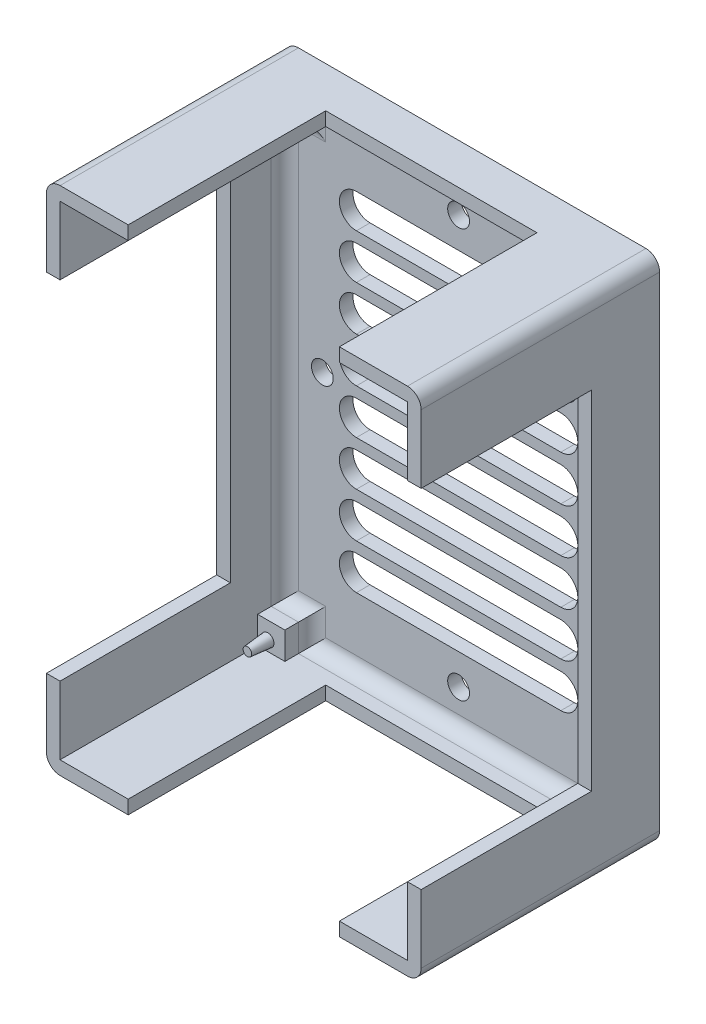
SolidWorks part; units mm, degrees
ref_plane "Front Plane" through (0, 0, 0) normal (1, 0, 0) x (0, 1, 0)
ref_plane "Top Plane" through (0, 0, 0) normal (0, 0, 1) x (0, 1, 0)
ref_plane "Right Plane" through (0, 0, 0) normal (0, 1, 0) x (-1, 0, 0)
sketch "Sketch1" plane through (0, 0, 0) normal (0, 0, 1) x (0, 1, 0)
  line L1 (0, 0) -> (71, 0)
  line L2 (0, 0) -> (0, 51)
  line L3 (0, 51) -> (71, 51)
  line L4 (71, 0) -> (71, 51)
  dimension "D1" = 71
  dimension "D2" = 51
extrude "Boss-Extrude1" add sketch "Sketch1" along normal blind 33
shell "Shell1" thickness 2 removed face at (-25.5, 35.5, 33) outward yes
sketch "Sketch3" plane through (-51, 0, 0) normal (1, 0, 0) x (0, 1, 0)
  line L0 (71, 33) -> (71, 0) construction
  line L1 (0, 4) -> (4, 4)
  line L2 (0, 4) -> (0, 0)
  line L3 (0, 0) -> (4, 0)
  line L4 (71, 4) -> (71, 0)
  line L5 (0, 33) -> (0, 0) construction
  line L7 (4, 4) -> (4, 0)
  line L8 (67, 4) -> (67, 0)
  line L9 (67, 4) -> (71, 4)
  line L10 (67, 0) -> (71, 0)
  line L11 (71, 0) -> (0, 0) construction
  dimension "D2" = 4
  dimension "D3" = 4
extrude "Boss-Extrude2" add sketch "Sketch3" along normal blind 4
ref_plane "Plane5" through (-25.5, 0, 0) normal (1, 0, 0) x (0, 0, -1)
ref_plane "Plane6" through (0, 35.5, 0) normal (0, 1, 0) x (1, 0, 0)
mirror "Mirror1" about plane through (-25.5, 0, 0) normal (1, 0, 0) of "Boss-Extrude2"
fillet "Fillet1" radius 2 16 edges at (-25.5, 0, 0) (-47, 2, 0) (-49, 4, 0) (-51, 35.5, 0) (-49, 67, 0) (-47, 69, 0) (-25.5, 71, 0) (-4, 69, 0) (-2, 67, 0) (0, 35.5, 0) (-2, 4, 0) (-4, 2, 0) (-53, -2, 15.5) (2, -2, 15.5) (-53, 73, 15.5) (2, 73, 15.5)
sketch "Sketch4" plane through (0, 0, 0) normal (0, 0, 1) x (1, 0, 0)
  line L0 (-40.5, 58.5) -> (-10.5, 58.5) construction
  line L1 (-40.5, 61) -> (-10.5, 61)
  line L2 (-40.5, 56) -> (-10.5, 56)
  line L3 (-6, 69) -> (-45, 69) construction
  line L4 (-25.5, 69) -> (-25.5, 2) construction
  line L5 (-45, 2) -> (-6, 2) construction
  line L6 (-40.5, 51.9286) -> (-10.5, 51.9286) construction
  line L7 (-40.5, 54.4286) -> (-10.5, 54.4286)
  line L8 (-40.5, 49.4286) -> (-10.5, 49.4286)
  line L9 (-40.5, 45.3571) -> (-10.5, 45.3571) construction
  line L10 (-40.5, 47.8571) -> (-10.5, 47.8571)
  line L11 (-40.5, 42.8571) -> (-10.5, 42.8571)
  line L12 (-40.5, 38.7857) -> (-10.5, 38.7857) construction
  line L13 (-40.5, 41.2857) -> (-10.5, 41.2857)
  line L14 (-40.5, 36.2857) -> (-10.5, 36.2857)
  line L15 (-40.5, 32.2143) -> (-10.5, 32.2143) construction
  line L16 (-40.5, 34.7143) -> (-10.5, 34.7143)
  line L17 (-40.5, 29.7143) -> (-10.5, 29.7143)
  line L18 (-40.5, 25.6429) -> (-10.5, 25.6429) construction
  line L19 (-40.5, 28.1429) -> (-10.5, 28.1429)
  line L20 (-40.5, 23.1429) -> (-10.5, 23.1429)
  line L21 (-40.5, 19.0714) -> (-10.5, 19.0714) construction
  line L22 (-40.5, 21.5714) -> (-10.5, 21.5714)
  line L23 (-40.5, 16.5714) -> (-10.5, 16.5714)
  line L24 (-40.5, 12.5) -> (-10.5, 12.5) construction
  line L25 (-40.5, 15) -> (-10.5, 15)
  line L26 (-40.5, 10) -> (-10.5, 10)
  line L27 (-45.5, 65.5) -> (-5.5, 65.5) construction
  line L28 (-45.5, 65.5) -> (-45.5, 5.5) construction
  line L29 (-45.5, 5.5) -> (-5.5, 5.5) construction
  line L30 (-5.5, 65.5) -> (-5.5, 5.5) construction
  line L31 (-49, 35.5) -> (-5, 35.5) construction
  line L32 (-49, 65) -> (-49, 6) construction
  arc A0 (-40.5, 61) -> (-40.5, 56) centre (-40.5, 58.5) ccw
  arc A1 (-10.5, 56) -> (-10.5, 61) centre (-10.5, 58.5) ccw
  arc A2 (-40.5, 54.4286) -> (-40.5, 49.4286) centre (-40.5, 51.9286) ccw
  arc A3 (-10.5, 49.4286) -> (-10.5, 54.4286) centre (-10.5, 51.9286) ccw
  arc A4 (-40.5, 47.8571) -> (-40.5, 42.8571) centre (-40.5, 45.3571) ccw
  arc A5 (-10.5, 42.8571) -> (-10.5, 47.8571) centre (-10.5, 45.3571) ccw
  arc A6 (-40.5, 41.2857) -> (-40.5, 36.2857) centre (-40.5, 38.7857) ccw
  arc A7 (-10.5, 36.2857) -> (-10.5, 41.2857) centre (-10.5, 38.7857) ccw
  arc A8 (-40.5, 34.7143) -> (-40.5, 29.7143) centre (-40.5, 32.2143) ccw
  arc A9 (-10.5, 29.7143) -> (-10.5, 34.7143) centre (-10.5, 32.2143) ccw
  arc A10 (-40.5, 28.1429) -> (-40.5, 23.1429) centre (-40.5, 25.6429) ccw
  arc A11 (-10.5, 23.1429) -> (-10.5, 28.1429) centre (-10.5, 25.6429) ccw
  arc A12 (-40.5, 21.5714) -> (-40.5, 16.5714) centre (-40.5, 19.0714) ccw
  arc A13 (-10.5, 16.5714) -> (-10.5, 21.5714) centre (-10.5, 19.0714) ccw
  arc A14 (-40.5, 15) -> (-40.5, 10) centre (-40.5, 12.5) ccw
  arc A15 (-10.5, 10) -> (-10.5, 15) centre (-10.5, 12.5) ccw
  circle A20 centre (-25.5, 5.5) radius 1.6
  circle A21 centre (-45.5, 35.5) radius 1.6
  circle A22 centre (-5.5, 35.5) radius 1.6
  circle A23 centre (-25.5, 65.5) radius 1.6
  point P2 (-25.5, 58.5)
  point P16 (-25.5, 51.9286)
  point P23 (-25.5, 45.3571)
  point P30 (-25.5, 38.7857)
  point P37 (-25.5, 32.2143)
  point P44 (-25.5, 25.6429)
  point P51 (-25.5, 19.0714)
  point P58 (-25.5, 12.5)
  dimension "D8" = 3.2
  dimension "D1" = 8
  dimension "D2" = 8
  dimension "D3" = 8
  dimension "D4" = 5
  dimension "D5" = 30
  dimension "D6" = 60
  dimension "D7" = 40
extrude "Cut-Extrude1" cut sketch "Sketch4" against normal up to next
sketch "Sketch5" plane through (2, 0, 0) normal (1, 0, 0) x (0, 1, 0)
  line L0 (0, 33) -> (71, 33) construction
  line L1 (10, 33) -> (61, 33)
  line L2 (10, 33) -> (10, 8)
  line L3 (10, 8) -> (61, 8)
  line L4 (61, 33) -> (61, 8)
  line L5 (35.5, 33) -> (35.5, -2) construction
  line L6 (0, -2) -> (71, -2) construction
  line L7 (71, -2) -> (71, 33) construction
  point P10 (0, 0)
  point P11 (60.1318, 13.1857)
  dimension "D1" = 10
  dimension "D2" = 10
extrude "Cut-Extrude2" cut sketch "Sketch5" against normal through all
sketch "Sketch6" plane through (0, -2, 0) normal (0, -1, 0) x (1, 0, 0)
  line L0 (-51, 33) -> (0, 33) construction
  line L1 (-41, 33) -> (-10, 33)
  line L2 (-41, 33) -> (-41, 4)
  line L3 (-41, 4) -> (-10, 4)
  line L4 (-10, 33) -> (-10, 4)
  line L5 (-25.5, 33) -> (-25.5, -2) construction
  line L6 (-51, -2) -> (0, -2) construction
  line L7 (0, -2) -> (0, 33) construction
  point P10 (0, 0)
  dimension "D1" = 6
  dimension "D2" = 10
extrude "Cut-Extrude3" cut sketch "Sketch6" against normal through all
sketch "Sketch7" plane through (0, 0, 4) normal (0, 0, 1) x (1, 0, 0)
  line L0 (-49.5, 35.5) -> (-1.5, 35.5) construction
  line L1 (-49.5, 69.5) -> (-1.5, 69.5) construction
  line L2 (-49.5, 69.5) -> (-49.5, 1.5) construction
  line L3 (-49.5, 1.5) -> (-1.5, 1.5) construction
  line L4 (-1.5, 69.5) -> (-1.5, 1.5) construction
  line L5 (-41, 71) -> (-10, 71) construction
  line L6 (-10, 0) -> (-41, 0) construction
  line L7 (-25.5, 69.5) -> (-25.5, 1.5) construction
  line L8 (0, 61) -> (0, 10) construction
  line L9 (-51, 10) -> (-51, 61) construction
  circle A0 centre (-49.5, 69.5) radius 0.9
  circle A1 centre (-1.5, 69.5) radius 0.9
  circle A2 centre (-1.5, 1.5) radius 0.9
  circle A3 centre (-49.5, 1.5) radius 0.9
  dimension "D1" = 1.8
  dimension "D2" = 48
  dimension "D3" = 68
extrude "Boss-Extrude3" add sketch "Sketch7" along normal blind 3 draft 5
equation "\"PCBWidth\"=50"
equation "\"D1@Sketch1\"=\"PCBLength\"+1mm"
equation "\"PCBLength\"=70"
equation "\"D1@Boss-Extrude1\" = \"PCBTop\" + \"PCBBottom\""
equation "\"PCBTop\"= 30"
equation "\"PCBBottom\"=3"
equation "\"D2@Sketch1\"=\"PCBWidth\"+1"
equation "\"SlotWidth\"= 6"
equation "\"SlotCount\"=4"
